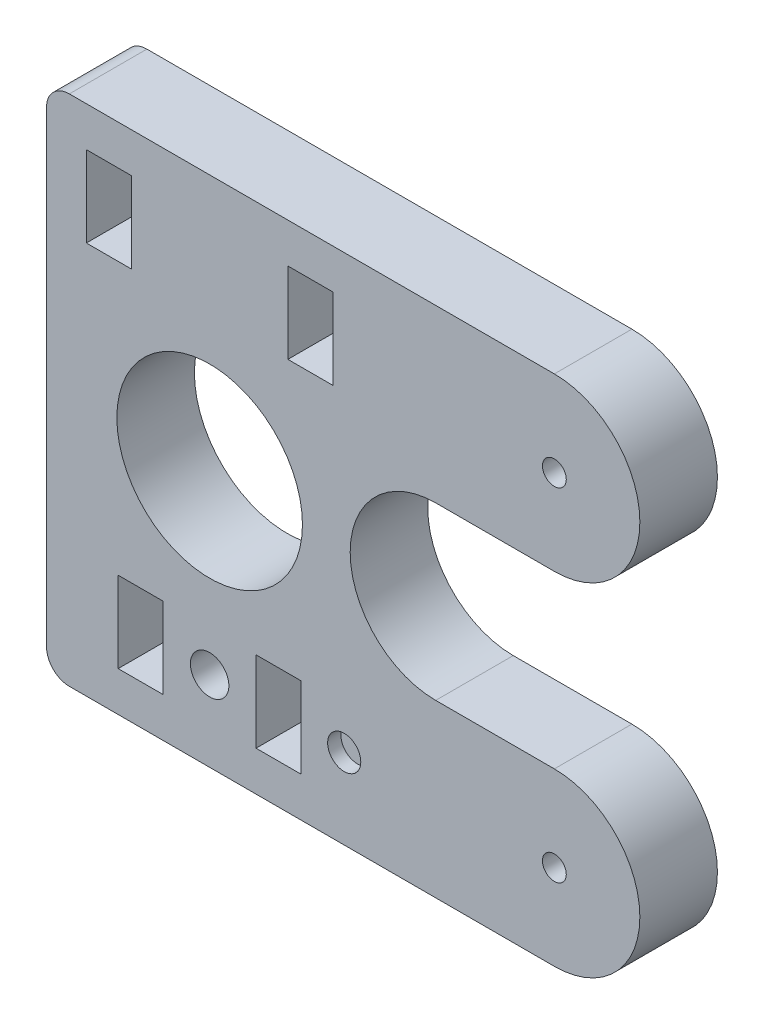
SolidWorks part; units mm, degrees
material "Acrylic (Medium-high impact)"
ref_plane "Front Plane" through (0, 0, 0) normal (0, 0, 1) x (1, 0, 0)
ref_plane "Top Plane" through (0, 0, 0) normal (0, 1, 0) x (1, 0, 0)
ref_plane "Right Plane" through (0, 0, 0) normal (1, 0, 0) x (0, 0, -1)
sketch "Sketch1" plane through (0, 0, 0) normal (0, 0, 1) x (1, 0, 0)
  line L0 (669.6368, 350.1155) -> (648.1438, 350.1155)
  line L1 (646.4265, 348.3982) -> (646.4265, 313.1328)
  line L2 (648.1438, 311.4155) -> (669.6368, 311.4155)
  line L3 (652.8265, 341.0155) -> (652.8265, 347.1155)
  line L4 (652.8265, 347.1155) -> (649.4265, 347.1155)
  line L5 (649.4265, 347.1155) -> (649.4265, 341.0155)
  line L6 (649.4265, 341.0155) -> (652.8265, 341.0155)
  line L7 (651.8265, 314.4155) -> (655.2265, 314.4155)
  line L8 (655.2265, 314.4155) -> (655.2265, 320.5155)
  line L9 (655.2265, 320.5155) -> (651.8265, 320.5155)
  line L10 (651.8265, 320.5155) -> (651.8265, 314.4155)
  line L11 (668.0265, 341.0155) -> (668.0265, 347.1155)
  line L12 (668.0265, 347.1155) -> (664.6265, 347.1155)
  line L13 (664.6265, 347.1155) -> (664.6265, 341.0155)
  line L14 (664.6265, 341.0155) -> (668.0265, 341.0155)
  line L15 (662.2265, 320.5155) -> (662.2265, 314.4155)
  line L16 (662.2265, 314.4155) -> (665.6265, 314.4155)
  line L17 (665.6265, 314.4155) -> (665.6265, 320.5155)
  line L18 (665.6265, 320.5155) -> (662.2265, 320.5155)
  line L19 (-318.0667, 330.7655) -> (49681.9333, 330.7655) construction
  line L21 (652.8265, 341.0155) -> (664.6265, 341.0155) construction
  line L22 (657.2765, 317.4655) -> (655.2265, 317.4655) construction
  line L23 (660.1765, 317.4655) -> (662.2265, 317.4655) construction
  line L24 (658.7265, -665.3806) -> (658.7265, 49334.6194) construction
  line L25 (669.6368, 311.4155) -> (684.7265, 311.4155)
  line L26 (669.6368, 350.1155) -> (684.7265, 350.1155)
  line L27 (684.7265, 317.8655) -> (684.7265, 330.7655) construction
  line L28 (684.7265, 330.7655) -> (684.7265, 343.6655) construction
  line L29 (684.7265, -669.9222) -> (684.7265, 49330.0778) construction
  line L30 (662.2265, 330.7655) -> (662.2265, 350.1155) construction
  line L31 (662.2265, 330.7655) -> (662.2265, 311.4155) construction
  line L32 (684.7265, 337.2155) -> (675.7765, 337.2155)
  line L33 (684.7265, 324.3155) -> (675.7765, 324.3155)
  circle A0 centre (684.7265, 343.6655) radius 0.9
  circle A1 centre (684.7265, 317.8655) radius 0.9
  arc A2 (684.7265, 311.4155) -> (684.7265, 324.3155) centre (684.7265, 317.8655) ccw
  circle A3 centre (658.7265, 317.4655) radius 1.45
  arc A4 (648.1438, 350.1155) -> (646.4265, 348.3982) centre (648.1438, 348.3982) ccw
  arc A5 (684.7265, 350.1155) -> (684.7265, 337.2155) centre (684.7265, 343.6655) cw
  arc A6 (675.7765, 337.2155) -> (675.7765, 324.3155) centre (675.7765, 330.7655) ccw
  arc A7 (646.4265, 313.1328) -> (648.1438, 311.4155) centre (648.1438, 313.1328) ccw
  circle A8 centre (658.7265, 330.7655) radius 7
  point P27 (658.7265, 341.0155)
  point P38 (669.3265, 330.7655)
  point P39 (665.7265, 330.7655)
  dimension "D5" = 2.9
  dimension "D12" = 3.6
  dimension "D13" = 14
  dimension "D14" = 1.8
  dimension "D15" = 1.7173
  dimension "D10" = 26
  dimension "D2" = 6.1
  dimension "D3" = 3.4
  dimension "D4" = 3.4
  dimension "D6" = 6.1
  dimension "D7" = 3
  dimension "D8" = 3
  dimension "D9" = 3
  dimension "D11" = 12.9
  dimension "D16" = 38.7
  dimension "D17" = 7
  dimension "D18" = 11.8
  dimension "Servo_length" = 20.5
extrude "Boss-Extrude2" add sketch "Sketch1" along normal blind 5.85
sketch "Sketch2" plane through (0, 0, 5.85) normal (0, 0, 1) x (1, 0, 0)
  line L0 (-341.2735, 317.4655) -> (49658.7265, 317.4655) construction
  line L1 (665.6265, 314.4155) -> (665.6265, 320.5155) construction
  circle A0 centre (668.8765, 317.4655) radius 1.25
  point P5 (667.6265, 317.4655)
  dimension "D1" = 2.5
  dimension "D2" = 2
extrude "Cut-Extrude1" cut sketch "Sketch2" against normal blind 1
